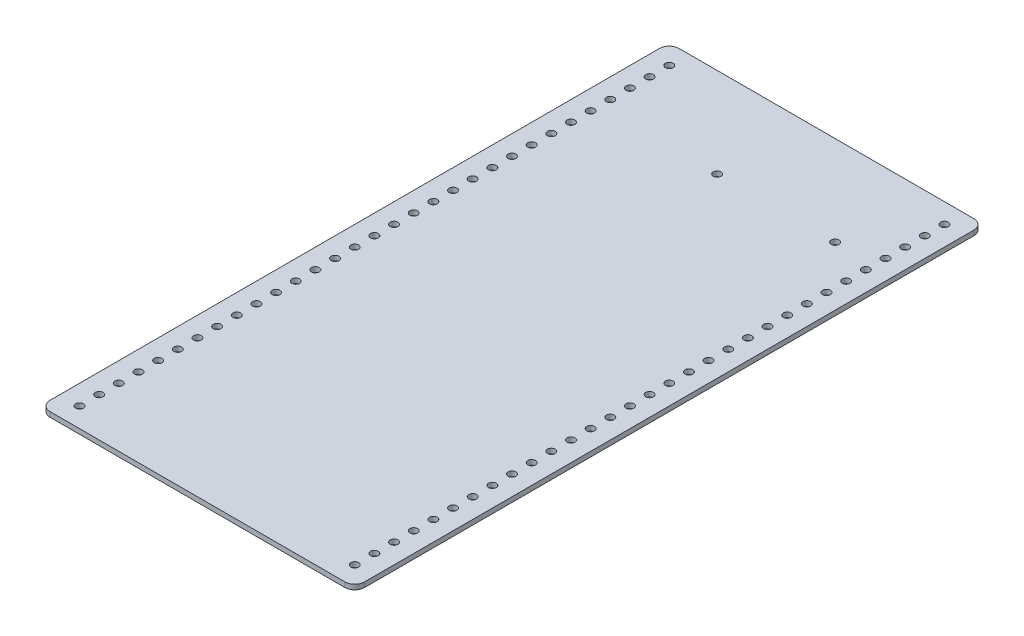
SolidWorks part; units mm, degrees
ref_plane "Front Plane" through (0, 0, 0) normal (0, 0, 1) x (1, 0, 0)
ref_plane "Top Plane" through (0, 0, 0) normal (0, 1, 0) x (1, 0, 0)
ref_plane "Right Plane" through (0, 0, 0) normal (1, 0, 0) x (0, 0, -1)
sketch "Sketch1" plane through (0, 0, 0) normal (0, 1, 0) x (1, 0, 0)
  line L1 (-77.8898, 288.009) -> (112.6102, 288.009)
  line L2 (-84.2398, 281.659) -> (-84.2398, -112.041)
  line L3 (-77.8898, -118.391) -> (112.6102, -118.391)
  line L4 (118.9602, 281.659) -> (118.9602, -112.041)
  arc A0 (-84.2398, -112.041) -> (-77.8898, -118.391) centre (-77.8898, -112.041) ccw
  arc A1 (112.6102, -118.391) -> (118.9602, -112.041) centre (112.6102, -112.041) ccw
  arc A2 (112.6102, 288.009) -> (118.9602, 281.659) centre (112.6102, 281.659) cw
  arc A3 (-77.8898, 288.009) -> (-84.2398, 281.659) centre (-77.8898, 281.659) ccw
  point P6 (-84.2398, -118.391)
  point P9 (118.9602, -118.391)
  point P14 (-84.2398, 288.009)
  dimension "D3" = 6.35
  dimension "D1" = 203.2
  dimension "D2" = 406.4
extrude "Boss-Extrude1" add sketch "Sketch1" along normal blind 3.175
sketch "Sketch3" plane through (0, 3.175, 0) normal (0, 1, 0) x (1, 0, 0)
  line L0 (118.9602, -112.041) -> (118.9602, 281.659) construction
  line L1 (112.6102, 288.009) -> (-77.8898, 288.009) construction
  line L2 (-84.2398, 281.659) -> (-84.2398, -112.041) construction
  circle A0 centre (-71.5398, 275.309) radius 2.5
  circle A1 centre (106.2602, 275.309) radius 2.5
  circle A2 centre (-71.5398, 262.609) radius 2.5
  circle A3 centre (106.2602, 262.609) radius 2.5
  circle A4 centre (-71.5398, 249.909) radius 2.5
  circle A5 centre (106.2602, 249.909) radius 2.5
  circle A6 centre (-71.5398, 237.209) radius 2.5
  circle A7 centre (106.2602, 237.209) radius 2.5
  circle A8 centre (-71.5398, 224.509) radius 2.5
  circle A9 centre (106.2602, 224.509) radius 2.5
  circle A10 centre (-71.5398, 211.809) radius 2.5
  circle A11 centre (106.2602, 211.809) radius 2.5
  circle A12 centre (-71.5398, 199.109) radius 2.5
  circle A13 centre (106.2602, 199.109) radius 2.5
  circle A14 centre (-71.5398, 186.409) radius 2.5
  circle A15 centre (106.2602, 186.409) radius 2.5
  circle A16 centre (-71.5398, 173.709) radius 2.5
  circle A17 centre (106.2602, 173.709) radius 2.5
  circle A18 centre (-71.5398, 161.009) radius 2.5
  circle A19 centre (106.2602, 161.009) radius 2.5
  circle A20 centre (-71.5398, 148.309) radius 2.5
  circle A21 centre (106.2602, 148.309) radius 2.5
  circle A22 centre (-71.5398, 135.609) radius 2.5
  circle A23 centre (106.2602, 135.609) radius 2.5
  circle A24 centre (-71.5398, 122.909) radius 2.5
  circle A25 centre (106.2602, 122.909) radius 2.5
  circle A26 centre (-71.5398, 110.209) radius 2.5
  circle A27 centre (106.2602, 110.209) radius 2.5
  circle A28 centre (-71.5398, 97.509) radius 2.5
  circle A29 centre (106.2602, 97.509) radius 2.5
  circle A30 centre (-71.5398, 84.809) radius 2.5
  circle A31 centre (106.2602, 84.809) radius 2.5
  circle A32 centre (-71.5398, 72.109) radius 2.5
  circle A33 centre (106.2602, 72.109) radius 2.5
  circle A34 centre (-71.5398, 59.409) radius 2.5
  circle A35 centre (106.2602, 59.409) radius 2.5
  circle A36 centre (-71.5398, 46.709) radius 2.5
  circle A37 centre (106.2602, 46.709) radius 2.5
  circle A38 centre (-71.5398, 34.009) radius 2.5
  circle A39 centre (106.2602, 34.009) radius 2.5
  circle A40 centre (-71.5398, 21.309) radius 2.5
  circle A41 centre (106.2602, 21.309) radius 2.5
  circle A42 centre (-71.5398, 8.609) radius 2.5
  circle A43 centre (106.2602, 8.609) radius 2.5
  circle A44 centre (-71.5398, -4.091) radius 2.5
  circle A45 centre (106.2602, -4.091) radius 2.5
  circle A46 centre (-71.5398, -16.791) radius 2.5
  circle A47 centre (106.2602, -16.791) radius 2.5
  circle A48 centre (-71.5398, -29.491) radius 2.5
  circle A49 centre (106.2602, -29.491) radius 2.5
  circle A50 centre (-71.5398, -42.191) radius 2.5
  circle A51 centre (106.2602, -42.191) radius 2.5
  circle A52 centre (-71.5398, -54.891) radius 2.5
  circle A53 centre (106.2602, -54.891) radius 2.5
  circle A54 centre (-71.5398, -67.591) radius 2.5
  circle A55 centre (106.2602, -67.591) radius 2.5
  circle A56 centre (-71.5398, -80.291) radius 2.5
  circle A57 centre (106.2602, -80.291) radius 2.5
  circle A58 centre (-71.5398, -92.991) radius 2.5
  circle A59 centre (106.2602, -92.991) radius 2.5
  circle A60 centre (-71.5398, -105.691) radius 2.5
  circle A61 centre (106.2602, -105.691) radius 2.5
  dimension "D1" = 5
  dimension "D2" = 5
  dimension "D3" = 12.7
  dimension "D4" = 12.7
  dimension "D5" = 12.7
  dimension "D6" = 12.7
  dimension "D7" = 31
extrude "Cut-Extrude2" cut sketch "Sketch3" against normal through all
sketch "Sketch7" plane through (0, 3.175, 0) normal (0, 1, 0) x (1, 0, 0)
  circle A0 centre (80.8952, 229.9938) radius 2.5 construction
  circle A1 centre (4.6952, 229.9938) radius 2.5 construction
  circle A2 centre (80.8952, 229.9938) radius 2.5
  circle A3 centre (4.6952, 229.9938) radius 2.5
extrude "Cut-Extrude5" cut sketch "Sketch7" against normal through all
